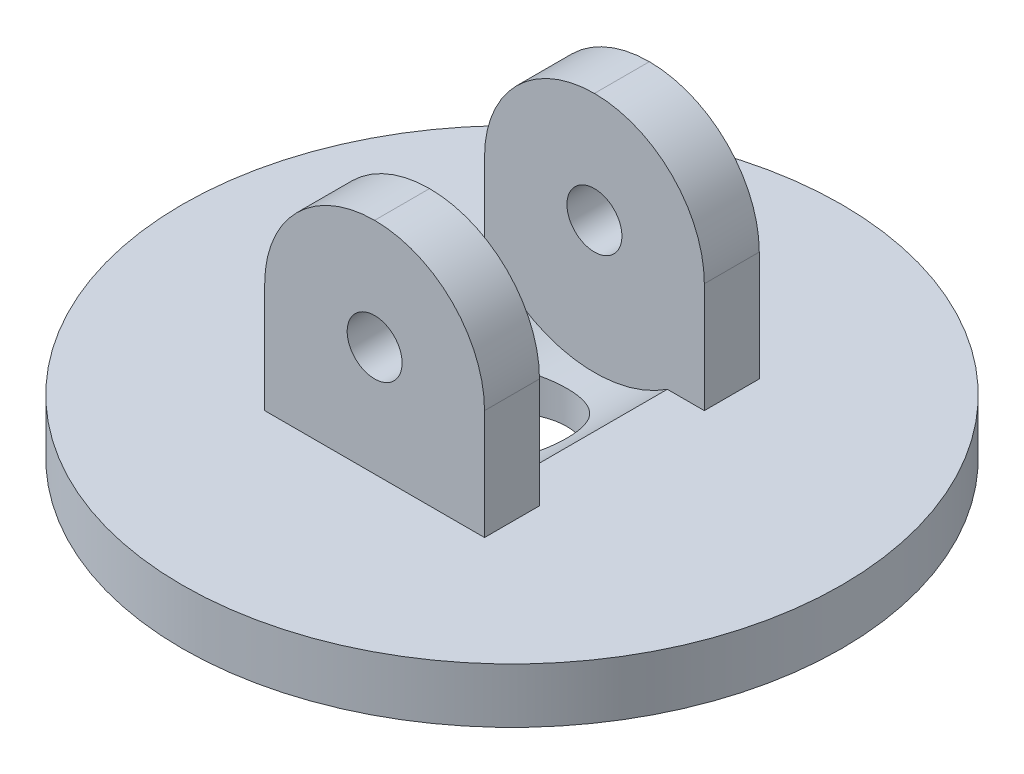
SolidWorks part; units mm, degrees
ref_plane "Ebene vorne" through (0, 0, 0) normal (0, 0, 1) x (1, 0, 0)
ref_plane "Ebene oben" through (0, 0, 0) normal (0, 1, 0) x (1, 0, 0)
ref_plane "Ebene rechts" through (0, 0, 0) normal (1, 0, 0) x (0, 0, -1)
sketch "Skizze1" plane through (0, 0, 0) normal (0, 1, 0) x (1, 0, 0)
  circle A0 centre (0, 0) radius 60
extrude "Aufsatz-Linear austragen1" add sketch "Skizze1" along normal blind 10
sketch "Skizze2" plane through (0, 10, 0) normal (0, 1, 0) x (1, 0, 0)
  line L0 (0, 0) -> (-60, 0) construction
  line L1 (-60, 0) -> (60, 0) construction
  line L2 (-35.6637, 25) -> (35.5893, 25) construction
  line L3 (-35.6637, -25) -> (35.5893, -25) construction
  line L4 (-20, -15) -> (20, -15)
  line L5 (-20, 25) -> (20, 25)
  line L6 (-20, 25) -> (-20, 15)
  line L7 (-20, 15) -> (20, 15)
  line L8 (20, 25) -> (20, 15)
  line L9 (20, -25) -> (20, -15)
  line L10 (-20, -25) -> (20, -25)
  line L11 (-20, -25) -> (-20, -15)
  circle A0 centre (0, 0) radius 60 construction
  dimension "D1" = 25
  dimension "D2" = 25
  dimension "D3" = 20
  dimension "D4" = 40
  dimension "D5" = 10
extrude "Aufsatz-Linear austragen2" add sketch "Skizze2" along normal blind 40
fillet "Verrundung1" radius 20 4 edges at (20, 50, -20) (20, 50, 20) (-20, 50, 20) (-20, 50, -20)
sketch "Skizze3" plane through (0, 0, -25) normal (0, 0, -1) x (-1, 0, 0)
  circle A0 centre (0, 30) radius 5
extrude "Schnitt-Linear austragen1" cut sketch "Skizze3" against normal through all
sketch "Skizze4" plane through (0, 10, 0) normal (0, 1, 0) x (1, 0, 0)
  circle A0 centre (0, 0) radius 10
extrude "Schnitt-Linear austragen2" cut sketch "Skizze4" against normal blind 10
sketch "Skizze5" plane through (0, 0, 15) normal (0, 0, -1) x (-1, 0, 0)
  circle A0 centre (0, 30) radius 24
extrude "Schnitt-Linear austragen3" cut sketch "Skizze5" along normal blind 30
